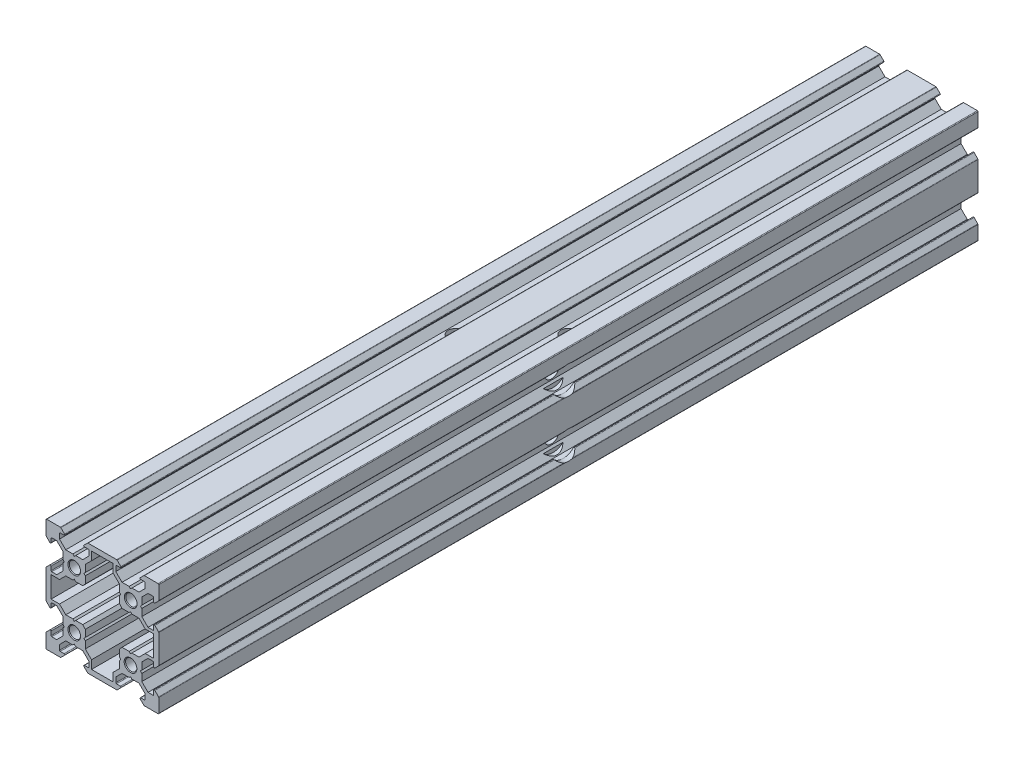
SolidWorks part; units mm, degrees
other "Marca1"
sketch "Croquis18" plane through (9.9172, 24.3141, -145) normal (0.9987, 0.0504, -0.0013) x (-0.0087, 0.1472, -0.9891)
ref_plane "Alzado" through (0, 0, 0) normal (0, 0, 1) x (1, 0, 0)
ref_plane "Planta" through (0, 0, 0) normal (0, 1, 0) x (1, 0, 0)
ref_plane "Vista lateral" through (0, 0, 0) normal (1, 0, 0) x (0, 0, -1)
sketch "Croquis1" plane through (0, 0, 0) normal (0, 0, 1) x (1, 0, 0)
  line L0 (-25.2101, -6.2) -> (-28.2, -6.2)
  line L1 (-13.8828, 8.2) -> (-6.2, 8.2)
  line L4 (-4.8096, 9.9268) -> (-3.5096, 8.6268)
  line L5 (-3.6864, 8.2) -> (-5.0429, 8.2)
  line L6 (-5.2929, 7.95) -> (-5.2929, 6.2)
  line L13 (-14.8728, 8.2) -> (-16.6, 8.2)
  line L14 (-5.2929, 6.2) -> (-3.0929, 4)
  line L15 (-3.0929, 4) -> (-0.5828, 4)
  line L16 (-16.0828, 0.5) -> (-16.5828, 0)
  line L17 (-16.0828, 3.0101) -> (-16.0828, 0.5)
  line L18 (-13.8828, 5.2101) -> (-16.0828, 3.0101)
  line L19 (-13.8828, 8.2) -> (-13.8828, 5.2101)
  line L23 (-16.0828, -3.0101) -> (-16.0828, -0.5)
  line L24 (-16.0828, -0.5) -> (-16.5828, 0)
  line L29 (-0.5828, 4) -> (-0.0828, 3.5)
  line L30 (-0.0828, 3.5) -> (0.4172, 4)
  line L31 (0.4172, 4) -> (2.9272, 4)
  line L32 (2.9272, 4) -> (5.1272, 6.2)
  line L33 (5.1272, 6.2) -> (5.1272, 7.95)
  line L34 (4.8772, 8.2) -> (3.5207, 8.2)
  line L35 (3.3439, 8.6268) -> (4.6439, 9.9268)
  line L36 (4.8207, 10) -> (9.6672, 10)
  line L37 (9.9172, 9.75) -> (9.9172, 4.9036)
  line L38 (9.8439, 4.7268) -> (8.5439, 3.4268)
  line L39 (8.1172, 3.6036) -> (8.1172, 4.9601)
  line L40 (7.8672, 5.2101) -> (6.1172, 5.2101)
  line L41 (6.1172, 5.2101) -> (3.9172, 3.0101)
  line L42 (3.9172, 3.0101) -> (3.9172, 0.5)
  line L43 (3.9172, 0.5) -> (3.4172, 0)
  line L44 (3.4172, 0) -> (3.9172, -0.5)
  line L45 (3.9172, -0.5) -> (3.9172, -3.0101)
  line L46 (3.9172, -3.0101) -> (6.1172, -5.2101)
  line L47 (6.1172, -5.2101) -> (7.8672, -5.2101)
  line L48 (8.1172, -4.9601) -> (8.1172, -3.6036)
  line L49 (8.5439, -3.4268) -> (9.8439, -4.7268)
  line L55 (5.1272, -6.2) -> (2.9272, -4)
  line L56 (2.9272, -4) -> (0.4172, -4)
  line L57 (0.4172, -4) -> (-0.0828, -3.5)
  line L58 (-0.0828, -3.5) -> (-0.5828, -4)
  line L59 (-0.5828, -4) -> (-3.0929, -4)
  line L66 (-4, -3.0101) -> (-4, -0.5)
  line L67 (-4, -0.5) -> (-3.5, 0)
  line L68 (-4, 0.5) -> (-3.5, 0)
  line L69 (-4, 3.0101) -> (-4, 0.5)
  line L70 (-6.2, 5.2101) -> (-4, 3.0101)
  line L71 (-6.2, 8.2) -> (-6.2, 5.2101)
  line L72 (-16.9899, -4) -> (-16.0828, -3.0101)
  line L78 (-4, -3.0101) -> (-3.0929, -4)
  line L164 (-26.2, 5.2101) -> (-24, 3.0101)
  line L165 (-24, 3.0101) -> (-24, 0.5)
  line L166 (-24, 0.5) -> (-23.5, 0)
  line L167 (-23.5, 0) -> (-24, -0.5)
  line L168 (-24, -0.5) -> (-24, -3.0101)
  line L169 (-24, -3.0101) -> (-26.2, -5.2101)
  line L170 (-26.2, -5.2101) -> (-27.95, -5.2101)
  line L171 (-28.2, -4.9601) -> (-28.2, -3.6036)
  line L172 (-28.6268, -3.4268) -> (-29.9268, -4.7268)
  line L178 (-25.2101, -6.2) -> (-23.0101, -4)
  line L179 (-23.0101, -4) -> (-20.5, -4)
  line L180 (-20.5, -4) -> (-20, -3.5)
  line L181 (-20, -3.5) -> (-19.5, -4)
  line L182 (-19.5, -4) -> (-16.9899, -4)
  line L228 (-4.9864, 10) -> (-15.0964, 10)
  line L229 (-15.2732, 9.9268) -> (-16.5732, 8.6268)
  line L230 (-16.3964, 8.2) -> (-15.0399, 8.2)
  line L231 (-14.7899, 7.95) -> (-14.7899, 6.2)
  line L232 (-14.7899, 6.2) -> (-16.9899, 4)
  line L233 (-16.9899, 4) -> (-19.5, 4)
  line L234 (-19.5, 4) -> (-20, 3.5)
  line L235 (-20, 3.5) -> (-20.5, 4)
  line L236 (-20.5, 4) -> (-23.0101, 4)
  line L237 (-23.0101, 4) -> (-25.2101, 6.2)
  line L238 (-25.2101, 6.2) -> (-25.2101, 7.95)
  line L239 (-24.9601, 8.2) -> (-23.6036, 8.2)
  line L240 (-23.4268, 8.6268) -> (-24.7268, 9.9268)
  line L241 (-24.9036, 10) -> (-29.75, 10)
  line L242 (-30, 9.75) -> (-30, 4.9036)
  line L243 (-29.9268, 4.7268) -> (-28.6268, 3.4268)
  line L244 (-28.2, 3.6036) -> (-28.2, 4.9601)
  line L245 (-27.95, 5.2101) -> (-26.2, 5.2101)
  line L256 (-29.9268, 0) -> (13.1752, 0) construction
  line L257 (-29.75, -19.9172) -> (9.6672, -19.9172) construction
  line L258 (-20, 14.7068) -> (-20, -27.5583) construction
  line L259 (-40.4121, -9.9586) -> (29.5949, -9.9586) construction
  line L260 (-0.0828, 12.632) -> (-0.0828, -27.5583) construction
  line L261 (-10.0414, -36.5607) -> (-10.0414, 12.632) construction
  line L262 (-30, -4.9036) -> (-30, -6.2)
  line L265 (9.9172, -6.2) -> (9.9172, -4.9036)
  line L267 (5.1272, -13.7172) -> (2.9272, -15.9172)
  line L268 (2.9272, -15.9172) -> (0.4172, -15.9172)
  line L269 (0.4172, -15.9172) -> (-0.0828, -16.4172)
  line L270 (-0.0828, -16.4172) -> (-0.5828, -15.9172)
  line L271 (-0.5828, -15.9172) -> (-3.0929, -15.9172)
  line L272 (-4, -16.9071) -> (-3.0929, -15.9172)
  line L273 (-4, -16.9071) -> (-4, -19.4172)
  line L274 (-4, -19.4172) -> (-3.5, -19.9172)
  line L275 (-4, -20.4172) -> (-3.5, -19.9172)
  line L276 (-4, -22.9272) -> (-4, -20.4172)
  line L277 (-6.2, -25.1272) -> (-4, -22.9272)
  line L278 (-6.2, -28.1172) -> (-6.2, -25.1272)
  line L279 (-13.8828, -28.1172) -> (-6.2, -28.1172)
  line L280 (-13.8828, -28.1172) -> (-13.8828, -25.1272)
  line L281 (-13.8828, -25.1272) -> (-16.0828, -22.9272)
  line L282 (-16.0828, -22.9272) -> (-16.0828, -20.4172)
  line L283 (-16.0828, -20.4172) -> (-16.5828, -19.9172)
  line L284 (-16.0828, -19.4172) -> (-16.5828, -19.9172)
  line L285 (-16.0828, -16.9071) -> (-16.0828, -19.4172)
  line L286 (-16.9899, -15.9172) -> (-16.0828, -16.9071)
  line L287 (-19.5, -15.9172) -> (-16.9899, -15.9172)
  line L288 (-20, -16.4172) -> (-19.5, -15.9172)
  line L289 (-20.5, -15.9172) -> (-20, -16.4172)
  line L290 (-23.0101, -15.9172) -> (-20.5, -15.9172)
  line L291 (-25.2101, -13.7172) -> (-23.0101, -15.9172)
  line L292 (-25.2101, -13.7172) -> (-28.2, -13.7172)
  line L294 (-30, -15.0136) -> (-30, -13.7172)
  line L295 (-28.6268, -16.4904) -> (-29.9268, -15.1904)
  line L296 (-28.2, -14.9571) -> (-28.2, -16.3136)
  line L297 (-26.2, -14.7071) -> (-27.95, -14.7071)
  line L298 (-24, -16.9071) -> (-26.2, -14.7071)
  line L299 (-24, -19.4172) -> (-24, -16.9071)
  line L300 (-23.5, -19.9172) -> (-24, -19.4172)
  line L301 (-24, -20.4172) -> (-23.5, -19.9172)
  line L302 (-24, -22.9272) -> (-24, -20.4172)
  line L303 (-26.2, -25.1272) -> (-24, -22.9272)
  line L304 (-27.95, -25.1272) -> (-26.2, -25.1272)
  line L305 (-28.2, -23.5207) -> (-28.2, -24.8772)
  line L306 (-29.9268, -24.6439) -> (-28.6268, -23.3439)
  line L307 (-30, -29.6672) -> (-30, -24.8207)
  line L308 (-24.9036, -29.9172) -> (-29.75, -29.9172)
  line L309 (-23.4268, -28.5439) -> (-24.7268, -29.8439)
  line L310 (-24.9601, -28.1172) -> (-23.6036, -28.1172)
  line L311 (-25.2101, -26.1172) -> (-25.2101, -27.8672)
  line L312 (-23.0101, -23.9172) -> (-25.2101, -26.1172)
  line L313 (-20.5, -23.9172) -> (-23.0101, -23.9172)
  line L314 (-20, -23.4172) -> (-20.5, -23.9172)
  line L315 (-19.5, -23.9172) -> (-20, -23.4172)
  line L316 (-16.9899, -23.9172) -> (-19.5, -23.9172)
  line L317 (-14.7899, -26.1172) -> (-16.9899, -23.9172)
  line L318 (-14.7899, -27.8672) -> (-14.7899, -26.1172)
  line L319 (-16.3964, -28.1172) -> (-15.0399, -28.1172)
  line L320 (-15.2732, -29.8439) -> (-16.5732, -28.5439)
  line L321 (-4.9864, -29.9172) -> (-15.0964, -29.9172)
  line L322 (-4.8096, -29.8439) -> (-3.5096, -28.5439)
  line L323 (-3.6864, -28.1172) -> (-5.0429, -28.1172)
  line L324 (-5.2929, -27.8672) -> (-5.2929, -26.1172)
  line L325 (-5.2929, -26.1172) -> (-3.0929, -23.9172)
  line L326 (-3.0929, -23.9172) -> (-0.5828, -23.9172)
  line L327 (-0.5828, -23.9172) -> (-0.0828, -23.4172)
  line L328 (-0.0828, -23.4172) -> (0.4172, -23.9172)
  line L329 (0.4172, -23.9172) -> (2.9272, -23.9172)
  line L330 (2.9272, -23.9172) -> (5.1272, -26.1172)
  line L331 (5.1272, -26.1172) -> (5.1272, -27.8672)
  line L332 (4.8772, -28.1172) -> (3.5207, -28.1172)
  line L333 (3.3439, -28.5439) -> (4.6439, -29.8439)
  line L334 (4.8207, -29.9172) -> (9.6672, -29.9172)
  line L335 (9.9172, -29.6672) -> (9.9172, -24.8207)
  line L336 (9.8439, -24.6439) -> (8.5439, -23.3439)
  line L337 (8.1172, -23.5207) -> (8.1172, -24.8772)
  line L338 (7.8672, -25.1272) -> (6.1172, -25.1272)
  line L339 (6.1172, -25.1272) -> (3.9172, -22.9272)
  line L340 (3.9172, -22.9272) -> (3.9172, -20.4172)
  line L341 (3.9172, -20.4172) -> (3.4172, -19.9172)
  line L342 (3.4172, -19.9172) -> (3.9172, -19.4172)
  line L343 (3.9172, -19.4172) -> (3.9172, -16.9071)
  line L344 (3.9172, -16.9071) -> (6.1172, -14.7071)
  line L345 (6.1172, -14.7071) -> (7.8672, -14.7071)
  line L346 (8.1172, -14.9571) -> (8.1172, -16.3136)
  line L347 (8.5439, -16.4904) -> (9.8439, -15.1904)
  line L348 (9.9172, -13.7172) -> (9.9172, -15.0136)
  line L349 (5.1272, -13.7172) -> (8.1172, -13.7172)
  line L350 (5.1272, -6.2) -> (8.1172, -6.2)
  line L351 (8.1172, -6.2) -> (8.1172, -13.7172)
  line L352 (9.9172, -13.7172) -> (9.9172, -6.2)
  line L353 (-30, -6.2) -> (-30, -13.7172)
  line L354 (-28.2, -13.7172) -> (-28.2, -6.2)
  arc A0 (-3.5096, 8.6268) -> (-3.6864, 8.2) centre (-3.6864, 8.45) cw
  arc A1 (-15.0964, 10) -> (-15.2732, 9.9268) centre (-15.0964, 9.75) ccw
  arc A2 (-15.0399, 8.2) -> (-14.7899, 7.95) centre (-15.0399, 7.95) cw
  arc A4 (-16.5732, 8.6268) -> (-16.3964, 8.2) centre (-16.3964, 8.45) ccw
  arc A13 (-29.9268, -4.7268) -> (-30, -4.9036) centre (-29.75, -4.9036) ccw
  arc A14 (-28.2, -3.6036) -> (-28.6268, -3.4268) centre (-28.45, -3.6036) ccw
  arc A15 (-27.95, -5.2101) -> (-28.2, -4.9601) centre (-27.95, -4.9601) cw
  arc A16 (-24.7268, 9.9268) -> (-24.9036, 10) centre (-24.9036, 9.75) ccw
  arc A17 (-23.6036, 8.2) -> (-23.4268, 8.6268) centre (-23.6036, 8.45) ccw
  arc A18 (-25.2101, 7.95) -> (-24.9601, 8.2) centre (-24.9601, 7.95) cw
  arc A19 (-28.2, 4.9601) -> (-27.95, 5.2101) centre (-27.95, 4.9601) cw
  arc A20 (-28.6268, 3.4268) -> (-28.2, 3.6036) centre (-28.45, 3.6036) ccw
  arc A21 (-30, 4.9036) -> (-29.9268, 4.7268) centre (-29.75, 4.9036) ccw
  arc A22 (-29.75, 10) -> (-30, 9.75) centre (-29.75, 9.75) ccw
  arc A23 (-5.0429, 8.2) -> (-5.2929, 7.95) centre (-5.0429, 7.95) ccw
  arc A24 (5.1272, 7.95) -> (4.8772, 8.2) centre (4.8772, 7.95) ccw
  arc A25 (3.5207, 8.2) -> (3.3439, 8.6268) centre (3.5207, 8.45) cw
  arc A26 (4.6439, 9.9268) -> (4.8207, 10) centre (4.8207, 9.75) cw
  arc A27 (9.6672, 10) -> (9.9172, 9.75) centre (9.6672, 9.75) cw
  arc A28 (9.9172, 4.9036) -> (9.8439, 4.7268) centre (9.6672, 4.9036) cw
  arc A29 (8.5439, 3.4268) -> (8.1172, 3.6036) centre (8.3672, 3.6036) cw
  arc A30 (8.1172, 4.9601) -> (7.8672, 5.2101) centre (7.8672, 4.9601) ccw
  arc A31 (7.8672, -5.2101) -> (8.1172, -4.9601) centre (7.8672, -4.9601) ccw
  arc A32 (8.1172, -3.6036) -> (8.5439, -3.4268) centre (8.3672, -3.6036) cw
  arc A33 (9.8439, -4.7268) -> (9.9172, -4.9036) centre (9.6672, -4.9036) cw
  arc A41 (-4.9864, 10) -> (-4.8096, 9.9268) centre (-4.9864, 9.75) cw
  arc A42 (-29.9268, -15.1904) -> (-30, -15.0136) centre (-29.75, -15.0136) cw
  arc A43 (-28.2, -16.3136) -> (-28.6268, -16.4904) centre (-28.45, -16.3136) cw
  arc A44 (-27.95, -14.7071) -> (-28.2, -14.9571) centre (-27.95, -14.9571) ccw
  arc A45 (-28.2, -24.8772) -> (-27.95, -25.1272) centre (-27.95, -24.8772) ccw
  arc A46 (-28.6268, -23.3439) -> (-28.2, -23.5207) centre (-28.45, -23.5207) cw
  arc A47 (-30, -24.8207) -> (-29.9268, -24.6439) centre (-29.75, -24.8207) cw
  arc A48 (-29.75, -29.9172) -> (-30, -29.6672) centre (-29.75, -29.6672) cw
  arc A49 (-24.7268, -29.8439) -> (-24.9036, -29.9172) centre (-24.9036, -29.6672) cw
  arc A50 (-23.6036, -28.1172) -> (-23.4268, -28.5439) centre (-23.6036, -28.3672) cw
  arc A51 (-25.2101, -27.8672) -> (-24.9601, -28.1172) centre (-24.9601, -27.8672) ccw
  arc A52 (-15.0399, -28.1172) -> (-14.7899, -27.8672) centre (-15.0399, -27.8672) ccw
  arc A53 (-16.5732, -28.5439) -> (-16.3964, -28.1172) centre (-16.3964, -28.3672) cw
  arc A54 (-15.0964, -29.9172) -> (-15.2732, -29.8439) centre (-15.0964, -29.6672) cw
  arc A55 (-4.9864, -29.9172) -> (-4.8096, -29.8439) centre (-4.9864, -29.6672) ccw
  arc A56 (-3.5096, -28.5439) -> (-3.6864, -28.1172) centre (-3.6864, -28.3672) ccw
  arc A57 (-5.0429, -28.1172) -> (-5.2929, -27.8672) centre (-5.0429, -27.8672) cw
  arc A58 (5.1272, -27.8672) -> (4.8772, -28.1172) centre (4.8772, -27.8672) cw
  arc A59 (3.5207, -28.1172) -> (3.3439, -28.5439) centre (3.5207, -28.3672) ccw
  arc A60 (4.6439, -29.8439) -> (4.8207, -29.9172) centre (4.8207, -29.6672) ccw
  arc A61 (9.6672, -29.9172) -> (9.9172, -29.6672) centre (9.6672, -29.6672) ccw
  arc A62 (9.9172, -24.8207) -> (9.8439, -24.6439) centre (9.6672, -24.8207) ccw
  arc A63 (8.5439, -23.3439) -> (8.1172, -23.5207) centre (8.3672, -23.5207) ccw
  arc A64 (8.1172, -24.8772) -> (7.8672, -25.1272) centre (7.8672, -24.8772) cw
  arc A65 (7.8672, -14.7071) -> (8.1172, -14.9571) centre (7.8672, -14.9571) cw
  arc A66 (8.1172, -16.3136) -> (8.5439, -16.4904) centre (8.3672, -16.3136) ccw
  arc A67 (9.8439, -15.1904) -> (9.9172, -15.0136) centre (9.6672, -15.0136) ccw
  point P134 (-10.0414, 8.2)
  dimension "D1" = 0.25
  dimension "D2" = 7.6828
  dimension "D3" = 10.1101
  dimension "D4" = 19.9172
  dimension "D5" = 19.9172
  dimension "D6" = 9.9586
  dimension "D7" = 9.9586
extrude "Saliente-Extruir1" add sketch "Croquis1" along normal blind 145 and the other way blind 145 contours A41 L228 L1 L71 L70 L69 L68 L67 L66 L23 L24 L16 L17 L18 L19 A1 L229 A4 L13 A2 L231 L232 L233 L234 L235 L236 L237 L238 A18 L239 A17 L240 A16 L241 A22 L242 A21 L243 A20 L244 region at (-4.5588, 8.8776, 0)
sketch "Croquis4" plane through (0, 0, 145) normal (0, 0, 1) x (1, 0, 0)
  line L0 (-24.6708, 0) -> (6.8007, 0) construction
  line L1 (-20, 3.5) -> (-20, 0) construction
  line L2 (-24.6708, -19.9172) -> (-20, -19.9172) construction
  line L3 (-20, -19.9172) -> (-20, -16.4172) construction
  line L4 (-0.0828, -16.4172) -> (-0.0828, -19.9172) construction
  line L5 (-0.0828, -19.9172) -> (3.4172, -19.9172) construction
  circle A0 centre (-20, 0) radius 2
  circle A1 centre (0, 0) radius 2
  circle A2 centre (-0.0828, -19.9172) radius 2
  circle A3 centre (-20, -19.9172) radius 2
  dimension "D1" = 4
extrude "Cortar-Extruir1" cut sketch "Croquis4" against normal through all
chamfer "Chaflán1" distance 0.25 angle 45 8 edges at (-18, 0, -145) (-18, -19.9172, -145) (2, 0, -145) (1.9172, -19.9172, -145) (1.9172, -19.9172, 145) (2, 0, 145) (-18, 0, 145) (-18, -19.9172, 145)
sketch "Croquis10" plane through (9.9172, 0, 0) normal (1, 0, 0) x (0, 0, -1)
  line L0 (0, 24.3141) -> (0, -44.9152) construction
  line L1 (145, 0) -> (-145, 0) construction
  line L2 (145, -19.9172) -> (-145, -19.9172) construction
  point P3 (0, 0)
  point P4 (0, -19.9172)
ref_plane "Plano1" through (0, -29.9172, 0) normal (0, -1, 0) x (-1, 0, 0)
sketch "Croquis13" plane through (0, -29.9172, 0) normal (0, -1, 0) x (1, 0, 0)
  line L0 (-0.0828, -145) -> (-0.0828, 145) construction
  line L1 (-20, -145) -> (-20, 145) construction
  line L2 (-4.9864, -145) -> (-15.0964, -145) construction
  line L3 (-4.9864, 145) -> (-15.0964, 145) construction
  point P0 (-0.0828, -10)
  point P1 (-20, 10)
  dimension "D1" = 135
  dimension "D2" = 135
hole_wizard "Refrentado para tornillo con cabeza hueca de M51" positions "Croquis14" profile "Croquis15" counterbore size "M5" standard "ISO" end condition through all
sketch "Croquis14" plane through (0, -29.9172, 0) normal (0, -1, 0) x (-1, 0, 0)
  point P0 (20, -10)
  point P3 (0.0828, 10)
sketch "Croquis15" plane through (-20, -29.9172, 10) normal (1, 0, 0) x (0, 0, -1)
  line L0 (0, 0) -> (0, 39.9172)
  line L1 (0, 39.9172) -> (2.65, 39.9172)
  line L3 (2.65, 39.9172) -> (2.65, 5.4)
  line L4 (2.65, 5.4) -> (5, 5.4)
  line L5 (5, 5.4) -> (5, 0)
  line L7 (5, 0) -> (0, 0)
  line L11 (0, -6.35) -> (0, 107.95) construction
  dimension "Diámetro de taladro hasta el siguiente" = 5.3
  dimension "Profundidad de taladro hasta el siguiente" = 39.9172
  dimension "Diámetro de refrentado" = 10
  dimension "Profundidad de refrentado" = 5.4
hole_wizard "Refrentado para tornillo con cabeza hueca de M52" positions "Croquis16" profile "Croquis17" counterbore size "M5" standard "ISO" end condition through all
sketch "Croquis16" plane through (9.9172, 0, 0) normal (1, 0, 0) x (0, 0, -1)
  point P0 (0, -19.9172)
  point P3 (0, 0)
sketch "Croquis17" plane through (9.9172, -19.9172, 0) normal (0, 1, 0) x (0, 0, -1)
  line L0 (0, 0) -> (0, 39.9172)
  line L1 (0, 39.9172) -> (2.65, 39.9172)
  line L3 (2.65, 39.9172) -> (2.65, 5.4)
  line L4 (2.65, 5.4) -> (5, 5.4)
  line L5 (5, 5.4) -> (5, 0)
  line L7 (5, 0) -> (0, 0)
  line L11 (0, -6.35) -> (0, 107.95) construction
  dimension "Diámetro de taladro hasta el siguiente" = 5.3
  dimension "Profundidad de taladro hasta el siguiente" = 39.9172
  dimension "Diámetro de refrentado" = 10
  dimension "Profundidad de refrentado" = 5.4
sketch "Croquis9" plane through (0, 10, 0) normal (0, 1, 0) x (1, 0, 0)
  line L0 (-0.0828, 7.35) -> (-0.0828, -145) construction
  line L1 (-4.9864, -145) -> (-15.0964, -145) construction
  circle A0 centre (-0.0828, -65) radius 2.25
  circle A1 centre (-0.0828, 85) radius 2.25
  point P0 (-0.0828, -65)
  point P1 (-0.0828, 85)
  dimension "D3" = 4.5
  dimension "D1" = 80
  dimension "D2" = 150
ref_plane "Plano2" through (0, 10, 0) normal (0, 1, 0) x (1, 0, 0)
ref_plane "Plano3" through (-30, 0, 0) normal (-1, 0, 0) x (0, 0, 1)
ref_plane "Plano4" through (9.9172, 0, 0) normal (1, 0, 0) x (0, 0, -1)
